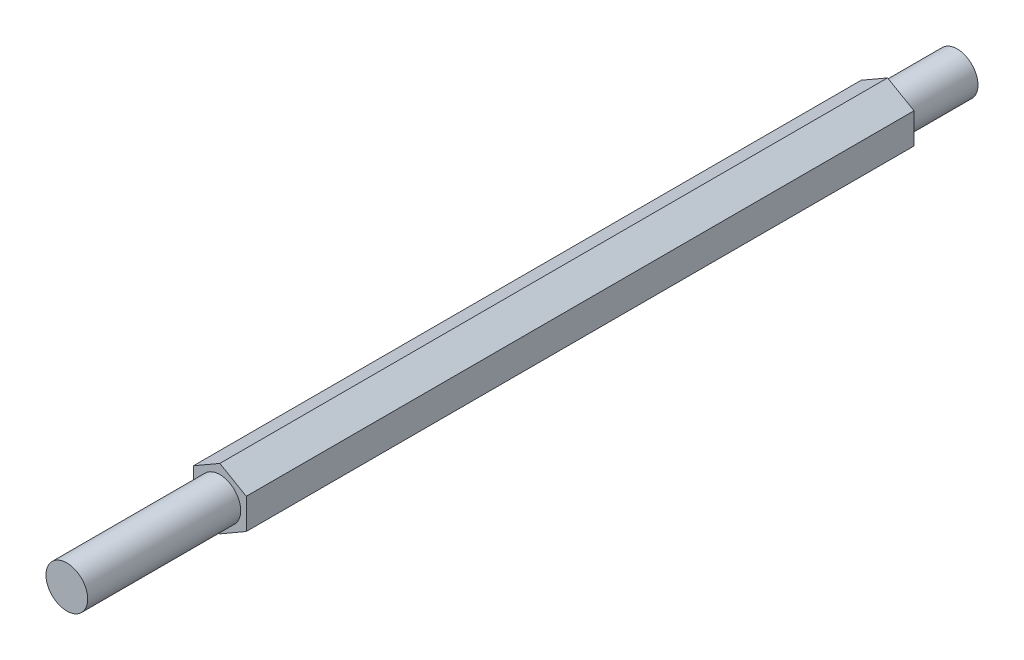
SolidWorks part; units mm, degrees
ref_plane "Plan de face" through (0, 0, 0) normal (0, 0, 1) x (1, 0, 0)
ref_plane "Plan de dessus" through (0, 0, 0) normal (0, 1, 0) x (1, 0, 0)
ref_plane "Plan de droite" through (0, 0, 0) normal (1, 0, 0) x (0, 0, -1)
sketch "Esquisse1" plane through (0, 0, 0) normal (0, 0, 1) x (1, 0, 0)
  line L1 (9.5, -5.4848) -> (9.5, 5.4848)
  line L2 (9.5, 5.4848) -> (0, 10.9697)
  line L3 (0, 10.9697) -> (-9.5, 5.4848)
  line L4 (-9.5, 5.4848) -> (-9.5, -5.4848)
  line L5 (-9.5, -5.4848) -> (0, -10.9697)
  line L6 (0, -10.9697) -> (9.5, -5.4848)
  circle A1 centre (0, 0) radius 9.5 construction
  dimension "D1" = 19
extrude "Boss.-Extru.1" add sketch "Esquisse1" along normal blind 320
sketch "Esquisse2" plane through (0, 0, 320) normal (0, 0, 1) x (1, 0, 0)
  circle A0 centre (0, 0) radius 7.5
  circle A1 centre (0, 0) radius 10.9697
  dimension "D1" = 15
extrude "Enlèv. mat.-Extru.1" cut sketch "Esquisse2" against normal blind 55
extrude "Enlèv. mat.-Extru.2" cut sketch "Esquisse2<2>" along normal blind 25 from surface starting at face at (0, 0, 0)
sketch "Esquisse2<2>" plane through (0, 0, 320) normal (0, 0, 1) x (1, 0, 0) same geometry as "Esquisse2"
